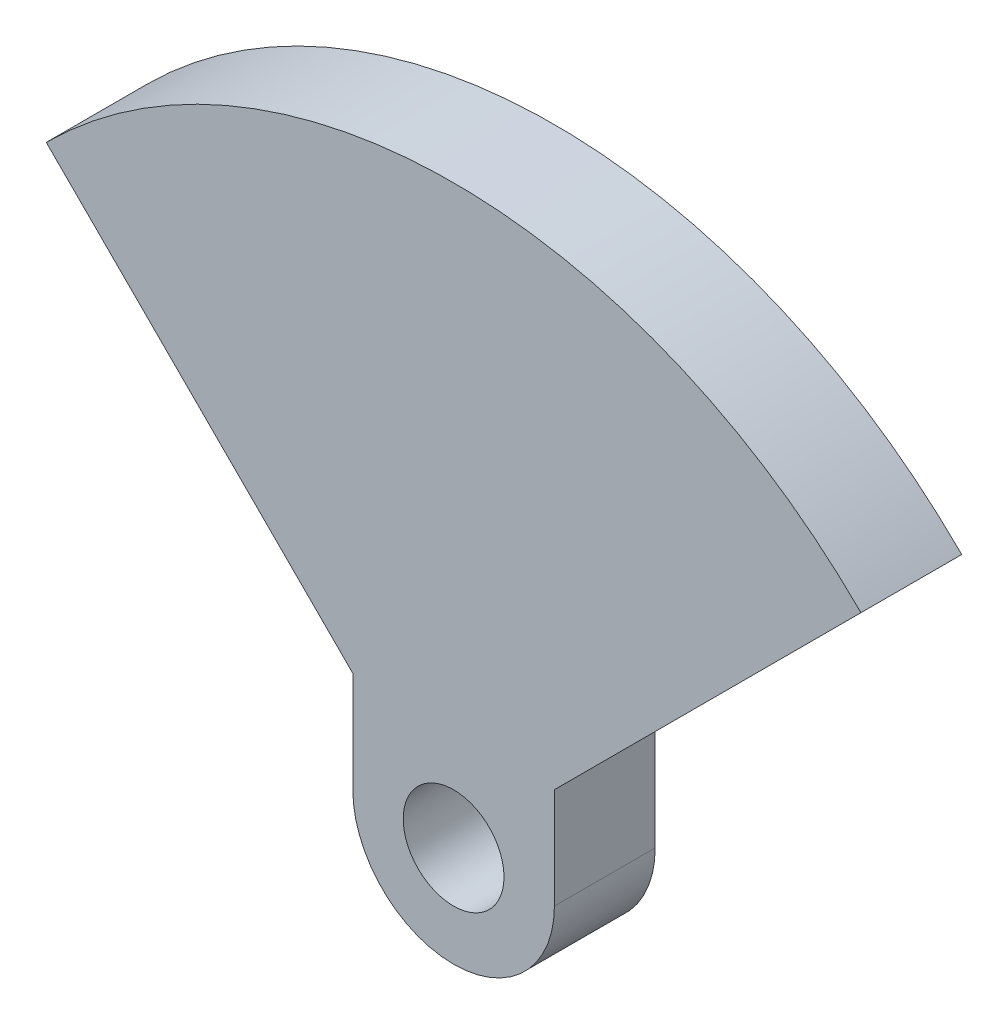
SolidWorks part; units mm, degrees
ref_plane "Front Plane" through (0, 0, 0) normal (0, 0, 1) x (1, 0, 0)
ref_plane "Top Plane" through (0, 0, 0) normal (0, 1, 0) x (1, 0, 0)
ref_plane "Right Plane" through (0, 0, 0) normal (1, 0, 0) x (0, 0, -1)
sketch "Sketch1" plane through (0, 0, 0) normal (0, 0, 1) x (1, 0, 0)
  line L0 (0, 0) -> (-2.1213, 2.1213)
  line L1 (0, 0) -> (2.1213, 2.1213)
  line L2 (-6, 0) -> (-6, 6)
  line L3 (6, 0) -> (6, 6)
  line L4 (-6, 6) -> (-24.2467, 24.2467)
  line L5 (6, 6) -> (24.2467, 24.2467)
  arc A0 (24.2467, 24.2467) -> (-24.2467, 24.2467) centre (0, 0) ccw
  circle A1 centre (0, 0) radius 3
  arc A2 (-6, 0) -> (6, 0) centre (0, 0) ccw
  dimension "D1" = 68.58
  dimension "D3" = 6
  dimension "D4" = 12
  dimension "D2" = 90
extrude "Boss-Extrude1" add sketch "Sketch1" along normal blind 6 contours L2 A2 L3 L5 A0 L4 A1 region at (0, 19.1691, 0)
equation "\"length\"= 2.7"
equation "\"D1@Sketch1\"=\"length\""
equation "\"dowel thick\"= 6mm"
equation "\"D3@Sketch1\"=\"dowel thick\""
equation "\"D4@Sketch1\"=\"dowel thick\"*2"
equation "\"D1@Boss-Extrude1\"=6mm"
